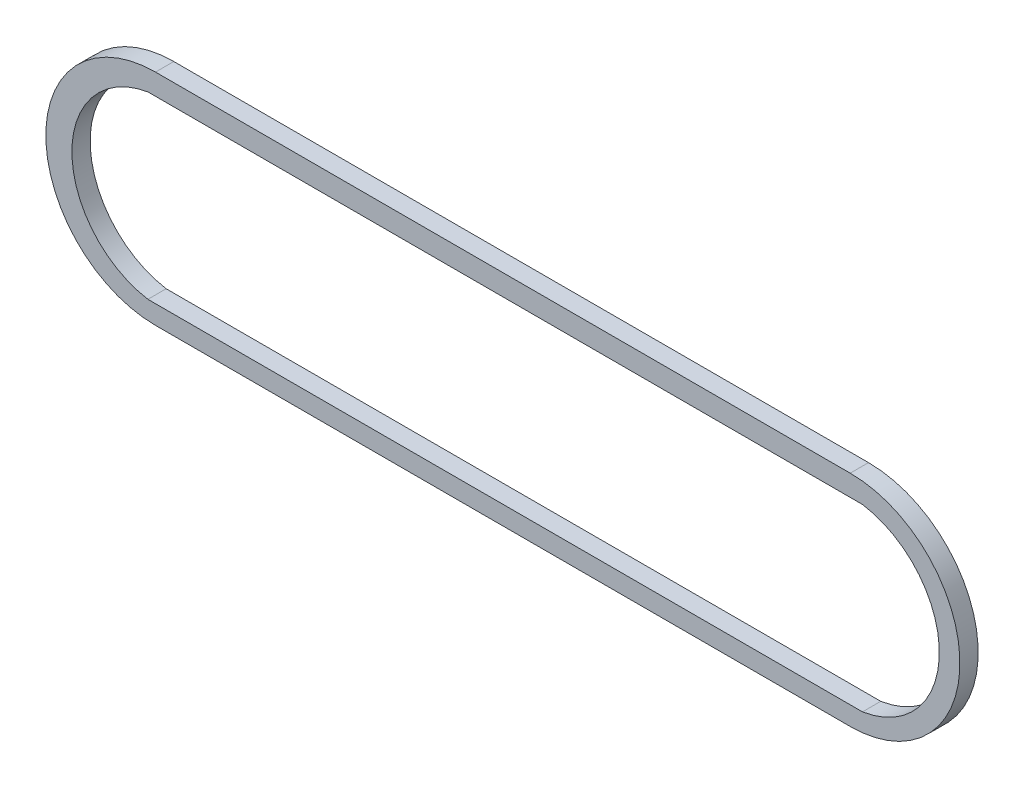
SolidWorks part; units mm, degrees
ref_plane "前视基准面" through (0, 0, 0) normal (0, 0, 1) x (1, 0, 0)
ref_plane "上视基准面" through (0, 0, 0) normal (0, 1, 0) x (1, 0, 0)
ref_plane "右视基准面" through (0, 0, 0) normal (1, 0, 0) x (0, 0, -1)
sketch "草图1" plane through (0, 0, 0) normal (0, 0, 1) x (1, 0, 0)
  line L1 (-73.5527, -24.213) -> (426.4473, -24.213)
  line L2 (-73.5527, -24.213) -> (-73.5527, 95.787)
  line L3 (-73.5527, 95.787) -> (426.4473, 95.787)
  line L4 (426.4473, -24.213) -> (426.4473, 95.787)
extrude "凸台-拉伸1" add sketch "草图1" along normal blind 10
fillet "圆角8" 2 edges at (-73.5527, 95.787, 5) (-73.5527, -24.213, 5) type full round first side face at (176.4473, 95.787, 5) second side face at (176.4473, -24.213, 5) middle face at (-73.5527, 35.787, 5)
fillet "圆角9" 2 edges at (426.4473, -24.213, 5) (426.4473, 95.787, 5) type full round first side face at (206.4473, -24.213, 5) second side face at (206.4473, 95.787, 5) middle face at (426.4473, 35.787, 5)
sketch "草图4" plane through (0, 0, 10) normal (0, 0, 1) x (1, 0, 0)
  line L0 (-17.716, 84.3032) -> (373.153, 84.3032)
  line L1 (-17.716, -13.9311) -> (373.153, -13.9311)
  arc A0 (373.153, 84.3032) -> (373.153, -13.9311) centre (365.4772, 35.1861) cw
  arc A1 (-17.716, 84.3032) -> (-17.716, -13.9311) centre (-9.4953, 35.1861) ccw
extrude "切除-拉伸1" cut sketch "草图4" against normal blind 10
